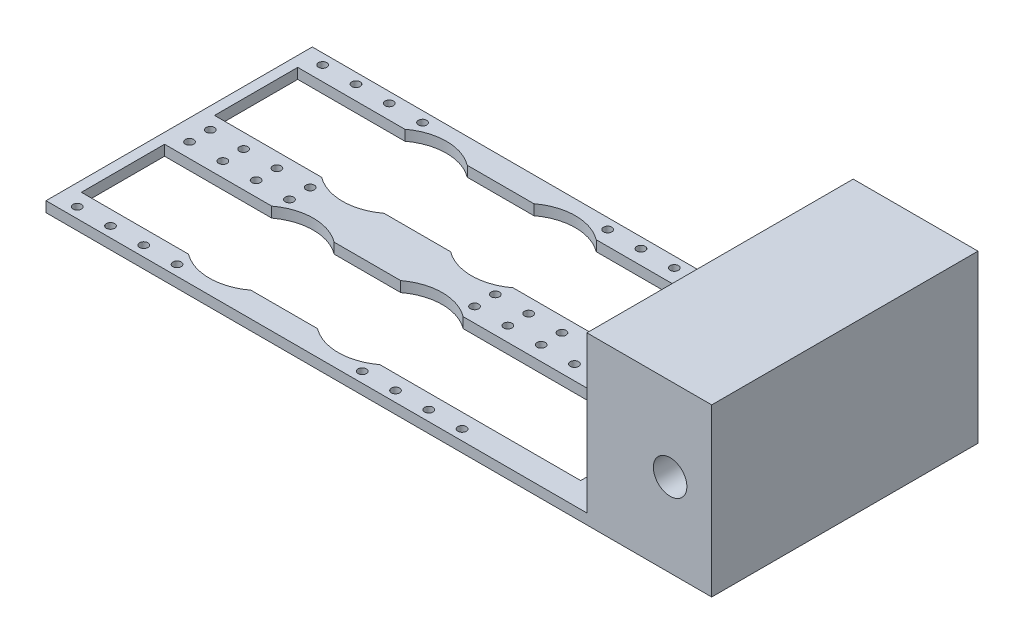
SolidWorks part; units mm, degrees
ref_plane "Front Plane" through (0, 0, 0) normal (0, 0, 1) x (1, 0, 0)
ref_plane "Top Plane" through (0, 0, 0) normal (0, 1, 0) x (1, 0, 0)
ref_plane "Right Plane" through (0, 0, 0) normal (1, 0, 0) x (0, 0, -1)
sketch "Sketch1" plane through (0, 0, 0) normal (0, 1, 0) x (1, 0, 0)
  line L1 (-80, 32) -> (80, 32)
  line L2 (-80, 32) -> (-80, -32)
  line L3 (-80, -32) -> (80, -32)
  line L4 (80, 32) -> (80, -32)
  line L5 (-80, 32) -> (80, -32) construction
  line L6 (-80, -32) -> (80, 32) construction
  point P0 (0, 0)
  dimension "D1" = 160
  dimension "D2" = 64
extrude "Boss-Extrude1" add sketch "Sketch1" along normal blind 40
sketch "Sketch2" plane through (0, 0, 32) normal (0, 0, 1) x (1, 0, 0)
  line L0 (80, 40) -> (80, 0) construction
  line L1 (-80, 40) -> (80, 40) construction
  line L2 (-80, 40) -> (50, 40)
  line L3 (-80, 40) -> (-80, 2.5)
  line L4 (-80, 2.5) -> (50, 2.5)
  line L5 (50, 40) -> (50, 2.5)
  line L6 (-80, 40) -> (50, 2.5) construction
  line L7 (-80, 2.5) -> (50, 40) construction
  line L8 (-80, 40) -> (-80, 0) construction
  circle A0 centre (70, 20) radius 4.025
  point P4 (80, 20)
  point P5 (-15, 21.25)
  dimension "D1" = 8.05
  dimension "D2" = 10
  dimension "D3" = 37.5
  dimension "D4" = 130
extrude "Cut-Extrude1" cut sketch "Sketch2" against normal through all
sketch "Sketch3" plane through (0, 40, 0) normal (0, 1, 0) x (1, 0, 0)
  line L0 (-80, 32) -> (-80, -32) construction
  line L1 (80, 32) -> (50, 32) construction
  line L2 (-75, 29.5) -> (-67, 29.5) construction
  line L3 (-75, 2.5) -> (-67, 2.5) construction
  line L4 (0, 0) -> (13.7346, 0) construction
  line L5 (-80, 32) -> (-80, -32) construction
  line L6 (-6.5, 29.5) -> (1.5, 29.5) construction
  line L7 (-75, 29.5) -> (-75, 2.5) construction
  line L8 (-77.5, 26) -> (42.5, 26)
  line L9 (-77.5, 26) -> (-77.5, 6)
  line L10 (-77.5, 6) -> (42.5, 6)
  line L11 (42.5, 26) -> (42.5, 6)
  line L12 (-6.5, 2.5) -> (1.5, 2.5) construction
  line L13 (-6.5, -2.5) -> (1.5, -2.5) construction
  line L14 (-75, -29.5) -> (-75, -2.5) construction
  line L15 (-6.5, -29.5) -> (1.5, -29.5) construction
  line L16 (-75, -2.5) -> (-67, -2.5) construction
  line L17 (-75, -29.5) -> (-67, -29.5) construction
  line L18 (42.5, -26) -> (42.5, -6)
  line L19 (-77.5, -6) -> (42.5, -6)
  line L20 (-77.5, -26) -> (-77.5, -6)
  line L21 (-77.5, -26) -> (42.5, -26)
  circle A0 centre (-75, 29.5) radius 1
  circle A1 centre (-75, 2.5) radius 1
  circle A2 centre (-67, 29.5) radius 1
  circle A3 centre (-59, 29.5) radius 1
  circle A4 centre (-51, 29.5) radius 1
  circle A11 centre (-67, 2.5) radius 1
  circle A12 centre (-59, 2.5) radius 1
  circle A13 centre (-51, 2.5) radius 1
  circle A50 centre (-6.5, 29.5) radius 1
  circle A51 centre (-6.5, 2.5) radius 1
  circle A52 centre (1.5, 29.5) radius 1
  circle A53 centre (9.5, 29.5) radius 1
  circle A54 centre (17.5, 29.5) radius 1
  circle A55 centre (1.5, 2.5) radius 1
  circle A56 centre (9.5, 2.5) radius 1
  circle A57 centre (17.5, 2.5) radius 1
  circle A58 centre (17.5, -2.5) radius 1
  circle A59 centre (9.5, -2.5) radius 1
  circle A60 centre (1.5, -2.5) radius 1
  circle A61 centre (17.5, -29.5) radius 1
  circle A62 centre (9.5, -29.5) radius 1
  circle A63 centre (1.5, -29.5) radius 1
  circle A64 centre (-6.5, -2.5) radius 1
  circle A65 centre (-6.5, -29.5) radius 1
  circle A66 centre (-51, -2.5) radius 1
  circle A67 centre (-59, -2.5) radius 1
  circle A68 centre (-67, -2.5) radius 1
  circle A69 centre (-51, -29.5) radius 1
  circle A70 centre (-59, -29.5) radius 1
  circle A71 centre (-67, -29.5) radius 1
  circle A72 centre (-75, -2.5) radius 1
  circle A73 centre (-75, -29.5) radius 1
  point P96 (-77.5, 16)
  point P97 (-75, 16)
  dimension "D1" = 2
  dimension "D3" = 2.5
  dimension "D4" = 27
  dimension "D12" = 2
  dimension "D18" = 5
  dimension "D2" = 5
  dimension "D6" = 8
  dimension "D8" = 8
  dimension "D9" = 20
  dimension "D10" = 120
  dimension "D11" = 2.5
  dimension "D13" = 44.5
  dimension "D15" = 8
  dimension "D17" = 8
  dimension "D5" = 4
  dimension "D7" = 4
  dimension "D14" = 4
  dimension "D16" = 4
extrude "Cut-Extrude2" cut sketch "Sketch3" against normal through all
sketch "Sketch4" plane through (0, 2.5, 0) normal (0, 1, 0) x (1, 0, 0)
  line L1 (-77.5, -6) -> (42.5, -6) construction
  line L2 (-77.5, 26) -> (42.5, 26) construction
  circle A0 centre (-44.25, -16) radius 12.5
  circle A1 centre (-51, -2.5) radius 1 construction
  circle A2 centre (-44.25, 16) radius 12.5
  circle A3 centre (-13.25, 16) radius 12.5
  circle A4 centre (-13.25, -16) radius 12.5
  circle A5 centre (-6.5, -2.5) radius 1 construction
  dimension "D1" = 25
  dimension "D4" = 6.75
  dimension "D2" = 6.75
  dimension "D3" = 10
  dimension "D5" = 10
extrude "Cut-Extrude3" cut sketch "Sketch4" against normal through all
sketch "Sketch5" plane through (0, 40, 0) normal (0, 1, 0) x (1, 0, 0)
  line L0 (80, 32) -> (50, 32) construction
  line L1 (45, 32) -> (80, 32)
  line L2 (45, 32) -> (45, -32)
  line L3 (45, -32) -> (80, -32)
  line L4 (80, 32) -> (80, -32)
  line L5 (45, 32) -> (80, -32) construction
  line L6 (45, -32) -> (80, 32) construction
  line L7 (42.5, -6) -> (42.5, -26) construction
  point P0 (62.5, 0)
  dimension "D1" = 2.5
